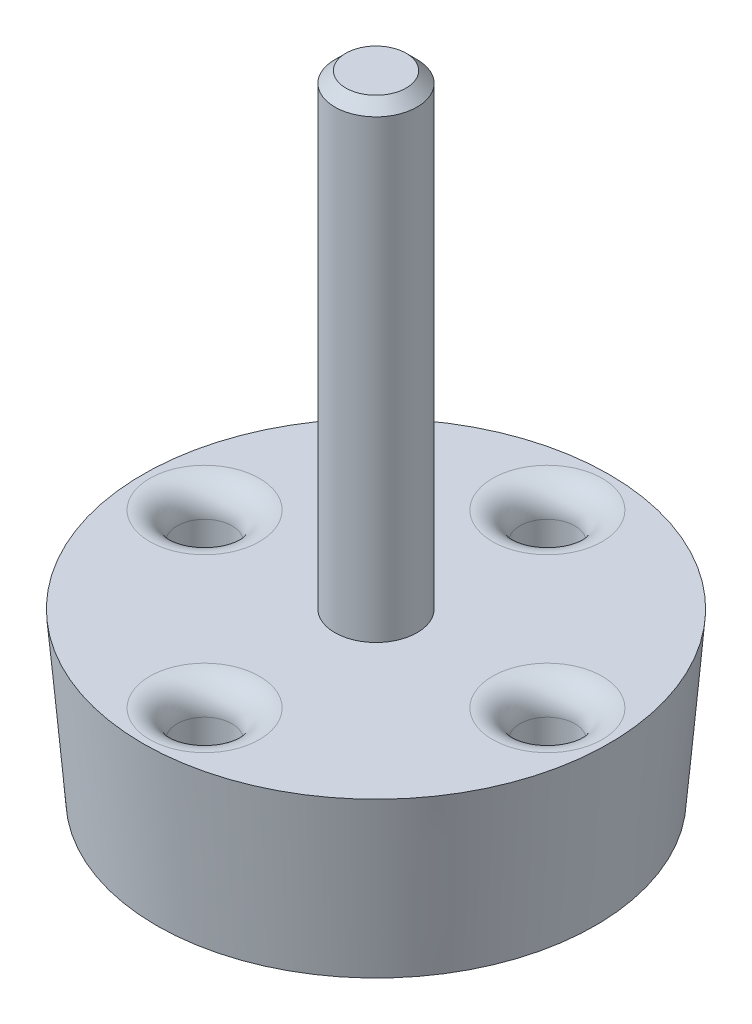
SolidWorks part; units mm, degrees
ref_plane "Front Plane" through (0, 0, 0) normal (0, 0, 1) x (1, 0, 0)
ref_plane "Top Plane" through (0, 0, 0) normal (0, 1, 0) x (1, 0, 0)
ref_plane "Right Plane" through (0, 0, 0) normal (1, 0, 0) x (0, 0, -1)
sketch "Sketch1" plane through (0, 0, 0) normal (0, 1, 0) x (1, 0, 0)
  circle A0 centre (0, 0) radius 8
  dimension "D1" = 16
ref_plane "Plane1" through (0, 6, 0) normal (0, 1, 0) x (1, 0, 0)
sketch "Sketch3" plane through (0, 6, 0) normal (0, 1, 0) x (1, 0, 0)
  circle A0 centre (0, 0) radius 8.5
  dimension "D1" = 17
loft "Loft1" add profiles "Sketch3", "Sketch1" connector at (4.7833, 6, 7.0264) connector at (4.6941, 0, 6.478)
sketch "Sketch4" plane through (0, 6, 0) normal (0, 1, 0) x (1, 0, 0)
  circle A0 centre (0, 0) radius 1.5
  dimension "D1" = 3
extrude "Boss-Extrude1" add sketch "Sketch4" along normal blind 17
sketch "Sketch5" plane through (0, 0, 0) normal (0, -1, 0) x (1, 0, 0)
  circle A0 centre (0, 0) radius 4.5
  dimension "D1" = 9
extrude "Cut-Extrude1" cut sketch "Sketch5" against normal blind 2
sketch "Sketch6" plane through (0, 0, 0) normal (0, -1, 0) x (1, 0, 0)
  circle A0 centre (0, 6.25) radius 1
  circle A2 centre (6.25, 0) radius 1
  circle A3 centre (0, -6.25) radius 1
  circle A4 centre (-6.25, 0) radius 1
  point P14 (0, 0)
  dimension "D1" = 2
  dimension "D3" = 6.25
  dimension "D2" = 4
extrude "Cut-Extrude4" cut sketch "Sketch6" against normal up to surface (6 mm away) up to face at (0, 6, 1.5)
sketch "Sketch8" plane through (0, 2, 0) normal (0, -1, 0) x (1, 0, 0)
  circle A0 centre (0, 0) radius 2
  dimension "D1" = 4
extrude "Cut-Extrude5" cut sketch "Sketch8" against normal blind 1
fillet "Fillet1" radius 1 1 edges at (0, 2, -2)
chamfer "Chamfer1" distance 0.4 angle 45 1 edges at (0, 23, 1.5)
fillet "Fillet2" radius 1 4 edges at (-6.25, 6, 1) (0, 6, 7.25) (6.25, 6, 1) (0, 6, -5.25)
